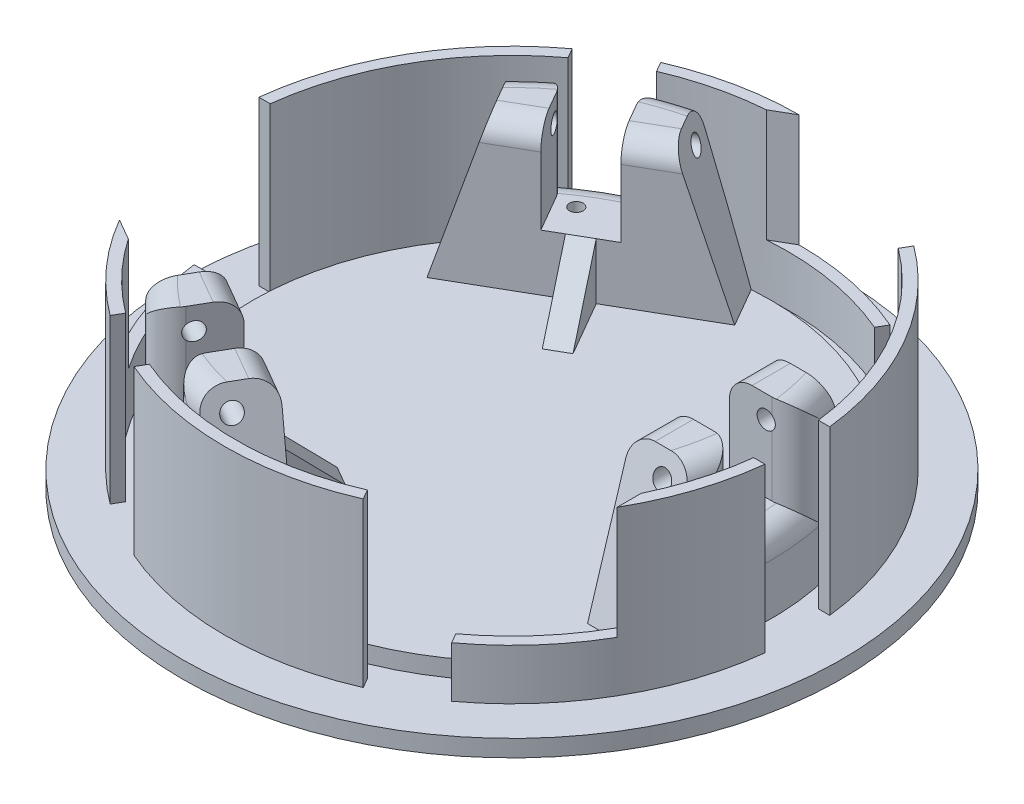
SolidWorks part; units mm, degrees
ref_plane "Front Plane" through (0, 0, 0) normal (0, 0, 1) x (1, 0, 0)
ref_plane "Top Plane" through (0, 0, 0) normal (0, 1, 0) x (1, 0, 0)
ref_plane "Right Plane" through (0, 0, 0) normal (1, 0, 0) x (0, 0, -1)
sketch "Sketch2" plane through (0, 0, 0) normal (0, 0, 1) x (1, 0, 0)
  line L0 (0, 0) -> (15, 0)
  line L1 (15, 0) -> (15, 14.5)
  line L2 (15, 14.5) -> (11, 14.5)
  line L3 (11, 14.5) -> (11, 1.5)
  line L4 (11, 1.5) -> (0, 1.5)
  line L5 (0, 1.5) -> (0, 0)
  dimension "D1" = 15
  dimension "D2" = 14.5
  dimension "D3" = 4
  dimension "D4" = 1.5
extrude "Boss-Extrude1" add sketch "Sketch2" along normal blind 20
ref_plane "Plane2" through (0, 0, 10) normal (0, 0, 1) x (1, 0, 0)
sketch "Sketch9" plane through (0, 1.5, 0) normal (0, 1, 0) x (1, 0, 0)
  line L0 (5.5, -20) -> (0, -12.5)
  line L1 (11, -20) -> (0, -20) construction
  line L2 (0, -20) -> (0, 0) construction
  line L3 (0, -12.5) -> (0, -7.5)
  line L4 (0, -7.5) -> (5.5, 0)
  line L5 (11, 0) -> (0, 0) construction
  line L6 (5.5, 0) -> (0, 0)
  line L7 (0, 0) -> (0, -20)
  line L8 (0, -20) -> (5.5, -20)
  point P14 (0, -10)
  point P15 (0, -10)
  line M3 (11, 0) -> (0, 0)
  line M4 (0, 0) -> (0, -20)
  line M5 (0, -20) -> (11, -20)
  dimension "D3" = 5
extrude "Cut-Extrude6" cut sketch "Sketch9" against normal through all contours L4 M4 M3 | L0 M5 M4 region at (1.8333, 1.5, 17.5) region at (1.8333, 1.5, 2.5)
sketch "Sketch10" plane through (11, 0, 0) normal (-1, 0, 0) x (0, 0, 1)
  line L0 (0, 1.5) -> (0, 14.5)
  line L1 (0, 14.5) -> (20, 14.5)
  line L2 (20, 14.5) -> (20, 1.5)
  line L3 (20, 1.5) -> (16, 14.5)
  line L4 (16, 14.5) -> (4, 14.5)
  line L5 (4, 14.5) -> (0, 1.5)
  line L6 (0, 1.5) -> (0.1757, 1.9576)
  line L7 (20, 14.5) -> (0, 14.5) construction
  line L8 (7.4, 14.5) -> (7.4, 6.5)
  line L9 (7.4, 6.5) -> (12.6, 6.5)
  line L10 (12.6, 6.5) -> (12.6, 14.5)
  point P4 (10, 6.5)
  point P13 (10, 14.5)
  point P14 (10, 14.5)
  line M1 (0, 14.5) -> (0, 1.5)
  line M3 (20, 1.5) -> (20, 14.5)
  line M4 (20, 14.5) -> (0, 14.5)
  dimension "D1" = 6
  dimension "D2" = 5.2
  dimension "D3" = 8
extrude "Cut-Extrude8" cut sketch "Sketch10" against normal through all contours L5 M4 M1 | L9 L10 L4 L8 | L3 M3 M4 region at (11, 10.1667, 18.6667) region at (11, 10.5, 10) region at (11, 10.1667, 1.3333)
sketch "Sketch12" plane through (0, 0, 10) normal (0, 0, 1) x (1, 0, 0)
  line L0 (5.377, 1.5) -> (11, 6.5)
  line L1 (5.5, 1.5) -> (0, 1.5) construction
  line L2 (11, 6.5) -> (11, 1.5)
  line L3 (11, 1.5) -> (5.377, 1.5)
extrude "Boss-Extrude3" add sketch "Sketch12" along normal mid plane 2
sketch "Sketch13" plane through (0, 0, 0) normal (0, 1, 0) x (1, 0, 0)
  line L0 (15, -20) -> (15, 0)
  arc A0 (15, 0) -> (15, -20) centre (-5.7123, -10) cw
  dimension "D1" = 23
extrude "Boss-Extrude4" add sketch "Sketch13" along normal up to surface (14.5 mm away) up to face at (13, 14.5, 5.7)
sketch "Sketch14" plane through (15, 0, 0) normal (-1, 0, 0) x (0, 0, 1)
  line L0 (16, 14.5) -> (20, 1.5)
  line L1 (20, 1.5) -> (20, 14.5)
  line L2 (20, 14.5) -> (16, 14.5)
  line L3 (4, 14.5) -> (0, 14.5)
  line L4 (0, 14.5) -> (0, 1.5)
  line L5 (0, 1.5) -> (4, 14.5)
  line L7 (7.4, 14.5) -> (12.6, 14.5)
  line L8 (7.4, 14.5) -> (7.4, 6.5)
  line L9 (7.4, 6.5) -> (12.6, 6.5)
  line L10 (12.6, 14.5) -> (12.6, 6.5)
extrude "Cut-Extrude10" cut sketch "Sketch14" against normal through all
sketch "Sketch15" plane through (0, 6.5, 0) normal (0, 1, 0) x (1, 0, 0)
  line L0 (11, -9) -> (11, 0) construction
  line L1 (17.1403, -7.4) -> (11, -7.4) construction
  circle A0 centre (14, -8.9) radius 0.6
  dimension "D1" = 1.2
  dimension "D2" = 3
  dimension "D3" = 1.5
extrude "Cut-Extrude11" cut sketch "Sketch15" against normal blind 25
fillet "Fillet1" radius 2 7 edges at (16.8798, 14.5, 5.6878) (16.8798, 14.5, 14.3122) (11, 14.5, 14.3) (11, 14.5, 5.7) (17.1403, 10.5, 7.4) (17.1403, 10.5, 12.6) (17.2877, 6.5, 10)
sketch "Sketch11" plane through (0, 0, 7.4) normal (0, 0, 1) x (1, 0, 0)
  line L0 (14.4123, 14.5) -> (13, 14.5) construction
  line L1 (11, 1.5) -> (11, 12.5) construction
  circle A0 centre (14.25, 12.5) radius 0.8
  dimension "D1" = 1.6
  dimension "D2" = 2
  dimension "D3" = 3.25
extrude "Cut-Extrude9" cut sketch "Sketch11" against normal through all both and the other way through all
sketch "Sketch16" plane through (0, 0, 0) normal (0, 1, 0) x (1, 0, 0)
  line L0 (0, -12.5) -> (0, -7.5) construction
  line L33 (-5.7123, 13) -> (-5.7123, -33) construction
  circle A0 centre (-5.7123, -10) radius 23
  circle A2 centre (-5.7123, -10) radius 29.2554
  arc A5 (16.7291, -15.0381) -> (16.7291, -4.9619) centre (-5.7123, -10) ccw construction
  point P7 (0, -10)
  dimension "D1" = 46
extrude "Boss-Extrude5" add sketch "Sketch16" against normal blind 1.5
sketch "Sketch22" plane through (0, -1.5, 0) normal (0, -1, 0) x (-1, 0, 0)
  circle A0 centre (5.7123, -10) radius 23
  dimension "D1" = 46
extrude "Boss-Extrude9" add sketch "Sketch22" against normal up to surface (1.5 mm away) up to face at (14, 0, 9.5)
sketch "Sketch23" plane through (0, 1.5, 0) normal (0, 1, 0) x (1, 0, 0)
  circle A0 centre (-5.7123, -10) radius 23
  arc A3 (-26.4246, 0) -> (15, -20) centre (-5.7123, -10) ccw construction
  dimension "D1" = 46
pattern_circular "CirPattern5" count 3 over 360 about axis through (-5.7123, 0, 10) along (0, 1, 0) of "Boss-Extrude1", "Cut-Extrude6", "Cut-Extrude8", "Boss-Extrude3", "Boss-Extrude4", "Cut-Extrude10", "Cut-Extrude11", "Fillet1", "Cut-Extrude9"
sketch "Sketch24" plane through (0, -1.5, 0) normal (0, -1, 0) x (1, 0, 0)
  circle A0 centre (-5.7123, 10) radius 23
  dimension "D1" = 46
extrude "Boss-Extrude10" add sketch "Sketch24" against normal up to surface (3 mm away) up to face at (6.5754, 1.5, 10)
sketch "Sketch25" plane through (0, -1.5, 0) normal (0, 1, 0) x (1, 0, 0)
  circle A0 centre (-5.7123, -10) radius 25.5
  circle A1 centre (-5.7123, -10) radius 24.5
  dimension "D1" = 51
  dimension "D2" = 49
extrude "Boss-Extrude11" add sketch "Sketch25" along normal up to surface (16 mm away) up to face at (-19.0426, 14.5, -5.1539)
sketch "Sketch26" plane through (0, 14.5, 0) normal (0, 1, 0) x (1, 0, 0)
  line L0 (29.0151, -7.125) -> (29.0151, -12.875)
  line L2 (11, -11) -> (11, -9) construction
  line L3 (11, -10) -> (29.0151, -10) construction
  line L4 (29.0151, -7.125) -> (17.7281, -7.125)
  line L5 (17.7281, -7.125) -> (17.7281, -12.875)
  line L6 (17.7281, -12.875) -> (29.0151, -12.875)
  dimension "D1" = 5.75
extrude "Cut-Extrude12" cut sketch "Sketch26" against normal up to surface (14.5 mm away) up to face at (-5.7123, 0, 33)
pattern_circular "CirPattern6" count 6 over 360 about axis through (-5.7123, 0, 10) along (0, 1, 0) of "Cut-Extrude12"
sketch "Sketch27" plane through (0, 14.5, 0) normal (0, 1, 0) x (1, 0, 0)
  line L0 (16.3713, -22.75) -> (16.3713, -20.6095)
  line L5 (8.9429, -29.6335) -> (9.4462, -30.5053) construction
  line L6 (8.9429, -29.6335) -> (9.4462, -30.5053)
  arc A1 (9.4462, -30.5053) -> (19.6251, -12.875) centre (-5.7123, -10) ccw construction
  arc A6 (8.9429, -29.6335) -> (18.6184, -12.875) centre (-5.7123, -10) ccw construction
  arc A7 (9.4462, -30.5053) -> (16.3713, -22.75) centre (-5.7123, -10) ccw
  arc A8 (8.9429, -29.6335) -> (16.3713, -20.6095) centre (-5.7123, -10) ccw
extrude "Cut-Extrude13" cut sketch "Sketch27" against normal blind 10
pattern_circular "CirPattern7" count 3 over 360 about axis through (-5.7123, 0, 10) along (0, 1, 0) of "Cut-Extrude13"
